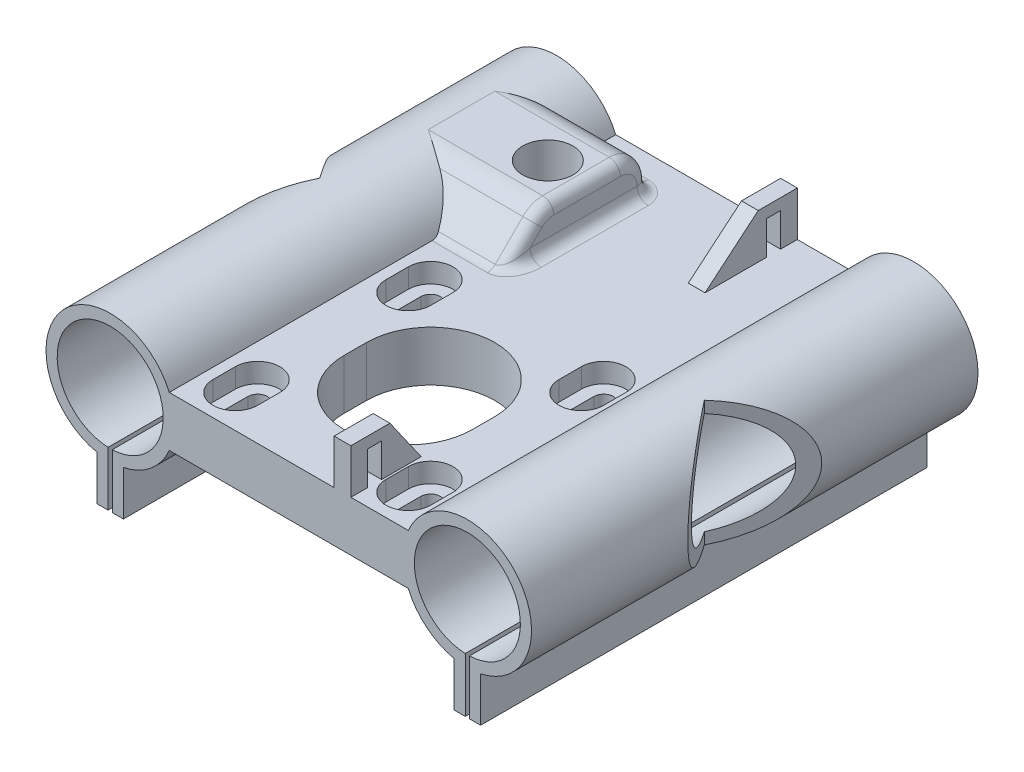
SolidWorks part; units mm, degrees
ref_plane "Front Plane" through (0, 0, 0) normal (0, 0, 1) x (1, 0, 0)
ref_plane "Top Plane" through (0, 0, 0) normal (0, 1, 0) x (1, 0, 0)
ref_plane "Right Plane" through (0, 0, 0) normal (1, 0, 0) x (0, 0, -1)
sketch "Sketch2" plane through (0, 0, 0) normal (0, 0, 1) x (1, 0, 0)
  line L0 (-51.5444, -8.3476) -> (12.4556, -8.3476) construction
  line L1 (-40.9614, -3.8476) -> (1.8726, -3.8476)
  line L2 (-40.9614, -12.8476) -> (1.8726, -12.8476)
  line L3 (-53.9194, -19.5997) -> (-53.9194, -27.5997)
  line L4 (-53.9194, -27.5997) -> (-51.9194, -27.5997)
  line L5 (-51.9194, -27.5997) -> (-51.9194, -17.8402)
  line L6 (-49.1694, -19.5997) -> (-49.1694, -27.5997)
  line L7 (-49.1694, -27.5997) -> (-51.1694, -27.5997)
  line L8 (-51.1694, -27.5997) -> (-51.1694, -17.8402)
  line L9 (-19.5444, -12.8476) -> (-19.5444, 19.6067) construction
  line L10 (14.8306, -19.5997) -> (14.8306, -27.5997)
  line L11 (14.8306, -27.5997) -> (12.8306, -27.5997)
  line L12 (12.8306, -27.5997) -> (12.8306, -17.8402)
  line L13 (12.0806, -27.5997) -> (12.0806, -17.8402)
  line L14 (10.0806, -27.5997) -> (12.0806, -27.5997)
  line L15 (10.0806, -19.5997) -> (10.0806, -27.5997)
  arc A0 (12.8306, -17.8402) -> (12.0806, -17.8402) centre (12.4556, -8.3476) ccw
  arc A1 (-51.1694, -17.8402) -> (-51.9194, -17.8402) centre (-51.5444, -8.3476) ccw
  arc A2 (14.8306, -19.5997) -> (1.8726, -3.8476) centre (12.4556, -8.3476) ccw
  arc A3 (-40.9614, -3.8476) -> (-53.9194, -19.5997) centre (-51.5444, -8.3476) ccw
  arc A4 (1.8726, -12.8476) -> (10.0806, -19.5997) centre (12.4556, -8.3476) ccw
  arc A5 (-49.1694, -19.5997) -> (-40.9614, -12.8476) centre (-51.5444, -8.3476) ccw
  dimension "D1" = 19
  dimension "D3" = 23
  dimension "D2" = 64
  dimension "D4" = 4.5
  dimension "D5" = 4.5
  dimension "D6" = 0.75
  dimension "D7" = 8
  dimension "D8" = 0.375
  dimension "D9" = 2
extrude "Boss-Extrude1" add sketch "Sketch2" along normal blind 80
sketch "Sketch3" plane through (0, -12.8476, 0) normal (0, -1, 0) x (1, 0, 0)
  line L0 (-40.9614, 80) -> (1.8726, 37.166) construction
  line L1 (1.8726, 80) -> (1.8726, 0) construction
  line L2 (1.8726, 80) -> (-40.9614, 37.166) construction
  line L3 (-40.9614, 80) -> (-40.9614, 0) construction
  line L4 (23.9556, 0) -> (23.9556, 80) construction
  line L5 (-40.7944, 79.833) -> (1.7056, 79.833) construction
  line L6 (-40.7944, 79.833) -> (-40.7944, 37.333) construction
  line L7 (-40.7944, 37.333) -> (1.7056, 37.333) construction
  line L8 (1.7056, 79.833) -> (1.7056, 37.333) construction
  line L9 (1.8726, 80) -> (23.9556, 80) construction
  line L10 (1.8726, 80) -> (1.8726, 52) construction
  line L11 (1.8726, 52) -> (23.9556, 52) construction
  line L12 (23.9556, 80) -> (23.9556, 52) construction
  line L13 (1.8726, 0) -> (23.9556, 0) construction
  line L14 (25.4556, 0) -> (1.8726, 0) construction
  line L15 (25.4556, 0) -> (25.4556, 28) construction
  line L16 (25.4556, 28) -> (1.8726, 28) construction
  line L17 (1.8726, 0) -> (1.8726, 28) construction
  line L18 (-4.0444, 74.083) -> (-4.0444, 70.083) construction
  line L19 (-2.2944, 74.083) -> (-2.2944, 70.083)
  line L20 (-5.7944, 74.083) -> (-5.7944, 70.083)
  line L21 (-35.0444, 74.083) -> (-35.0444, 70.083) construction
  line L22 (-33.2944, 74.083) -> (-33.2944, 70.083)
  line L23 (-36.7944, 74.083) -> (-36.7944, 70.083)
  line L24 (-4.0444, 43.083) -> (-4.0444, 39.083) construction
  line L25 (-2.2944, 43.083) -> (-2.2944, 39.083)
  line L26 (-5.7944, 43.083) -> (-5.7944, 39.083)
  line L27 (-35.0444, 43.083) -> (-35.0444, 39.083) construction
  line L28 (-33.2944, 43.083) -> (-33.2944, 39.083)
  line L29 (-36.7944, 43.083) -> (-36.7944, 39.083)
  line L30 (-19.5444, 58.583) -> (-19.5444, 54.583) construction
  line L31 (-8.0444, 58.583) -> (-8.0444, 54.583)
  line L32 (-31.0444, 58.583) -> (-31.0444, 54.583)
  circle A0 centre (-35.0444, 74.083) radius 1.7859 construction
  circle A1 centre (-4.0444, 74.083) radius 1.6904 construction
  circle A2 centre (-4.0444, 43.083) radius 1.6904 construction
  circle A3 centre (-35.0444, 43.083) radius 1.75 construction
  circle A4 centre (-19.5444, 58.583) radius 11.5 construction
  arc A5 (-2.2944, 74.083) -> (-5.7944, 74.083) centre (-4.0444, 74.083) ccw
  arc A6 (-5.7944, 70.083) -> (-2.2944, 70.083) centre (-4.0444, 70.083) ccw
  arc A7 (-33.2944, 74.083) -> (-36.7944, 74.083) centre (-35.0444, 74.083) ccw
  arc A8 (-36.7944, 70.083) -> (-33.2944, 70.083) centre (-35.0444, 70.083) ccw
  arc A9 (-2.2944, 43.083) -> (-5.7944, 43.083) centre (-4.0444, 43.083) ccw
  arc A10 (-5.7944, 39.083) -> (-2.2944, 39.083) centre (-4.0444, 39.083) ccw
  arc A11 (-33.2944, 43.083) -> (-36.7944, 43.083) centre (-35.0444, 43.083) ccw
  arc A12 (-36.7944, 39.083) -> (-33.2944, 39.083) centre (-35.0444, 39.083) ccw
  arc A13 (-8.0444, 58.583) -> (-31.0444, 58.583) centre (-19.5444, 58.583) ccw
  arc A14 (-31.0444, 54.583) -> (-8.0444, 54.583) centre (-19.5444, 54.583) ccw
  point P35 (-4.0444, 72.083)
  point P41 (-35.0444, 72.083)
  point P47 (-4.0444, 41.083)
  point P53 (-35.0444, 41.083)
  point P59 (-19.5444, 56.583)
  dimension "D6" = 3.5
  dimension "D7" = 31
  dimension "D8" = 31
  dimension "D9" = 23
  dimension "D10" = 1.75
  dimension "D12" = 1.75
  dimension "D14" = 1.75
  dimension "D16" = 1.75
  dimension "D18" = 11.5
  dimension "D1" = 45
  dimension "D2" = 45
  dimension "D3" = 42.5
  dimension "D4" = 28
  dimension "D5" = 28
  dimension "D11" = 4
  dimension "D13" = 4
  dimension "D15" = 4
  dimension "D17" = 4
  dimension "D19" = 4
ref_plane "Plane1" through (-9.9194, 0, 0) normal (-1, 0, 0) x (0, 0, 1)
sketch "Sketch4" plane through (-9.9194, 0, 0) normal (-1, 0, 0) x (0, 0, 1)
  line L0 (40, 3.1524) -> (40, -35.757) construction
  line L1 (80, 3.1524) -> (0, 3.1524) construction
  line L2 (80, -3.8476) -> (80, 4.1524)
  line L3 (80, -19.5997) -> (80, 3.1524) construction
  line L4 (80, 4.1524) -> (73, 4.1524)
  line L5 (73, 4.1524) -> (67.3983, -3.8476)
  line L6 (80, -3.8476) -> (0, -3.8476) construction
  line L7 (67.3983, -3.8476) -> (74.5, -3.8476)
  line L8 (0, -3.8476) -> (0, 4.1524)
  line L9 (77, 2.1524) -> (74.5, 2.1524)
  line L10 (77, 2.1524) -> (77, -3.8476)
  line L11 (3, -3.8476) -> (0, -3.8476)
  line L12 (74.5, 2.1524) -> (74.5, -3.8476)
  line L13 (3, 2.1524) -> (3, -3.8476)
  line L14 (5.5, 2.1524) -> (5.5, -3.8476)
  line L15 (3, 2.1524) -> (5.5, 2.1524)
  line L16 (0, 4.1524) -> (7, 4.1524)
  line L17 (7, 4.1524) -> (16.534, -3.8476)
  line L18 (16.534, -3.8476) -> (5.5, -3.8476)
  line L20 (77, -3.8476) -> (80, -3.8476)
  dimension "D1" = 8
  dimension "D2" = 7
  dimension "D3" = 55
  dimension "D4" = 6
  dimension "D5" = 40
  dimension "D6" = 3
  dimension "D7" = 2.5
extrude "Boss-Extrude2" add sketch "Sketch4" along normal blind 1.5 and the other way blind 1.5 contours L12 L9 L10 L7 L2 L4 L5 | L18 L17 L16 L8 L11 L13 L15 L14 region at (-9.9194, -3.6983, 78.5) region at (-9.9194, -0.3006, 6.576)
extrude "Cut-Extrude1" cut sketch "Sketch3" against normal up to surface (9 mm away) up to face at (-13.1277, -3.8476, 40)
sketch "Sketch8" plane through (0, -3.8476, 0) normal (0, 1, 0) x (1, 0, 0)
  line L0 (-4.0444, -74.083) -> (-4.0444, -70.083) construction
  line L1 (-8.0444, -74.083) -> (-8.0444, -70.083)
  line L2 (-0.0444, -74.083) -> (-0.0444, -70.083)
  line L3 (-4.0444, -43.083) -> (-4.0444, -39.083) construction
  line L4 (-8.0444, -43.083) -> (-8.0444, -39.083)
  line L5 (-0.0444, -43.083) -> (-0.0444, -39.083)
  line L6 (-35.0444, -43.083) -> (-35.0444, -39.083) construction
  line L7 (-39.0444, -43.083) -> (-39.0444, -39.083)
  line L8 (-31.0444, -43.083) -> (-31.0444, -39.083)
  line L9 (-35.0444, -74.083) -> (-35.0444, -70.083) construction
  line L10 (-39.0444, -74.083) -> (-39.0444, -70.083)
  line L11 (-31.0444, -74.083) -> (-31.0444, -70.083)
  arc A0 (-8.0444, -74.083) -> (-0.0444, -74.083) centre (-4.0444, -74.083) ccw
  arc A1 (-0.0444, -70.083) -> (-8.0444, -70.083) centre (-4.0444, -70.083) ccw
  arc A2 (-8.0444, -43.083) -> (-0.0444, -43.083) centre (-4.0444, -43.083) ccw
  arc A3 (-0.0444, -39.083) -> (-8.0444, -39.083) centre (-4.0444, -39.083) ccw
  arc A4 (-39.0444, -43.083) -> (-31.0444, -43.083) centre (-35.0444, -43.083) ccw
  arc A5 (-31.0444, -39.083) -> (-39.0444, -39.083) centre (-35.0444, -39.083) ccw
  arc A6 (-39.0444, -74.083) -> (-31.0444, -74.083) centre (-35.0444, -74.083) ccw
  arc A7 (-31.0444, -70.083) -> (-39.0444, -70.083) centre (-35.0444, -70.083) ccw
  point P4 (-4.0444, -72.083)
  point P13 (-4.0444, -41.083)
  point P18 (-35.0444, -41.083)
  point P27 (-35.0444, -72.083)
  dimension "D1" = 4
extrude "Cut-Extrude2" cut sketch "Sketch8" against normal blind 3.5
sketch "Sketch7" plane through (0, -12.8476, 0) normal (0, -1, 0) x (1, 0, 0)
  circle A0 centre (-19.5444, 58.583) radius 11 construction
  circle A1 centre (-36.0444, 17.083) radius 33.5 construction
  circle A2 centre (-36.0444, 17.083) radius 4.5
  dimension "D1" = 67
  dimension "D2" = 22
  dimension "D4" = 9
  dimension "D3" = 16.5
  dimension "D5" = 41.5
extrude "Cut-Extrude5" cut sketch "Sketch7" against normal up to surface (9 mm away) up to face at (-35.0444, -3.8476, 72.083)
sketch "Sketch9" plane through (0, -27.5997, 0) normal (0, -1, 0) x (1, 0, 0)
  line L0 (1.8726, 80) -> (1.8726, 0) construction
  line L1 (23.9556, 80) -> (1.8726, 80) construction
  line L2 (23.9556, 80) -> (23.9556, 52) construction
  line L3 (23.9556, 52) -> (1.8726, 52) construction
  line L4 (1.8726, 80) -> (1.8726, 52) construction
  line L5 (-40.9614, 80) -> (-40.9614, 0) construction
  line L6 (23.9556, 0) -> (1.8726, 0) construction
  line L7 (23.9556, 0) -> (23.9556, 28) construction
  line L8 (23.9556, 28) -> (1.8726, 28) construction
  line L9 (1.8726, 0) -> (1.8726, 28) construction
  line L10 (-63.0444, 0) -> (-40.9614, 0) construction
  line L11 (-63.0444, 0) -> (-63.0444, 28) construction
  line L12 (-63.0444, 28) -> (-40.9614, 28) construction
  line L13 (-40.9614, 0) -> (-40.9614, 28) construction
  line L14 (23.9556, 52) -> (14.913, 40)
  line L15 (-63.0444, 80) -> (-40.9614, 80) construction
  line L16 (-63.0444, 80) -> (-63.0444, 52) construction
  line L17 (-63.0444, 52) -> (-40.9614, 52) construction
  line L18 (-40.9614, 80) -> (-40.9614, 52) construction
  line L19 (23.9556, 28) -> (14.913, 40)
  line L20 (-63.0444, 28) -> (-54.0017, 40)
  line L21 (-63.0444, 52) -> (-54.0017, 40)
  line L22 (-63.0444, 80) -> (-63.0444, 0) construction
  line L23 (23.9556, 52) -> (23.9556, 28)
  line L24 (-63.0444, 52) -> (-63.0444, 28)
  dimension "D1" = 28
  dimension "D2" = 37
  dimension "D3" = 53
  dimension "D4" = 53
  dimension "D5" = 53
extrude "Cut-Extrude6" cut sketch "Sketch9" against normal blind 57
sketch "Sketch10" [suppressed] plane through (0, -12.8476, 0) normal (0, -1, 0) x (1, 0, 0)
  line L0 (-40.9614, 80) -> (-40.9614, 0) construction
  line L1 (-40.9614, 33.583) -> (1.8726, 33.583) construction
  line L2 (-40.9614, 33.583) -> (-40.9614, 0.583) construction
  line L3 (-40.9614, 0.583) -> (1.8726, 0.583) construction
  line L4 (1.8726, 33.583) -> (1.8726, 0.583) construction
  circle A0 centre (-36.0444, 17.083) radius 4.5 construction
  dimension "D1" = 33
  dimension "D2" = 16.5
ref_axis "Axis1" through (-36.0444, -3.8476, 17.083) along (0, -1, 0)
ref_plane "Plane2" through (0, 0, 17.083) normal (0, 0, -1) x (-1, 0, 0)
sketch "Sketch11" plane through (0, 0, 17.083) normal (0, 0, -1) x (-1, 0, 0)
  line L0 (36.0444, -3.8476) -> (36.0444, -12.8476) construction
  line L1 (40.9614, -3.8476) -> (29.0444, -3.8476)
  line L3 (40.9614, 3.1524) -> (29.0444, 3.1524)
  line L4 (29.0444, -3.8476) -> (29.0444, 3.1524)
  line L5 (51.5444, 3.1524) -> (40.9614, 3.1524)
  arc A0 (51.5444, 3.1524) -> (40.9614, -3.8476) centre (51.5444, -8.3476) ccw
  dimension "D1" = 7
extrude "Boss-Extrude3" add sketch "Sketch11" along normal blind 11 and the other way blind 15
chamfer "Chamfer1" distance 7 angle 45 1 edges at (-40.2944, 3.1524, 32.083)
fillet "Fillet1" radius 5 1 edges at (-40.2944, 3.1524, 25.083)
sketch "Sketch12" plane through (0, 3.1524, 0) normal (0, 1, 0) x (1, 0, 0)
  circle A0 centre (-36.0444, -17.083) radius 4.5
extrude "Cut-Extrude7" cut sketch "Sketch12" against normal up to surface (16 mm away) up to face at (-36.0444, -12.8476, 12.583)
fillet "Fillet2" radius 5 1 edges at (-40.2944, 3.1524, 6.083)
fillet "Fillet3" radius 2 7 edges at (-35.0029, -3.8476, 32.083) (-29.0444, -3.8476, 19.083) (-29.0444, -1.0798, 29.3152) (-29.0444, 2.7718, 24.9254) (-29.0444, 1.6879, 7.5475) (-29.0444, 3.1524, 17.0475) (-35.0029, -3.8476, 6.083)
